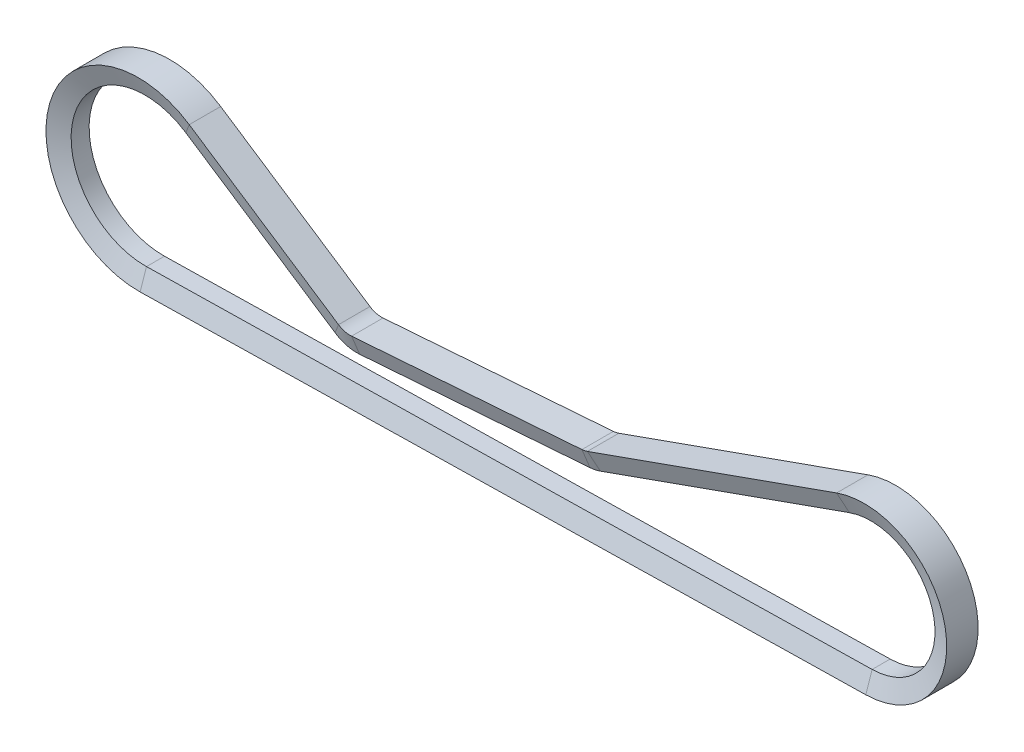
SolidWorks part; units mm, degrees
ref_plane "Front Plane" through (0, 0, 0) normal (0, 0, 1) x (1, 0, 0)
ref_plane "Top Plane" through (0, 0, 0) normal (0, 1, 0) x (1, 0, 0)
ref_plane "Right Plane" through (0, 0, 0) normal (1, 0, 0) x (0, 0, -1)
sketch "Sketch2" plane through (0, 0, 0) normal (0, 0, 1) x (1, 0, 0)
  line L0 (0, 0) -> (1, 0) construction
  line L1 (0, 0) -> (0, 1) construction
  line L12 (0.4814, -24.9954) -> (-219.4574, -29.231)
  line L14 (-204.5678, 22.1295) -> (-159.3267, -7.744)
  line L15 (-155.3616, -8.7779) -> (-85.5504, -3.6396)
  line L16 (-83.8896, -3.2899) -> (-8.3741, 23.5558)
  arc A4 (-219.4574, -29.231) -> (-204.5678, 22.1295) centre (-219.9965, -1.2362) cw
  arc A7 (-8.3741, 23.5558) -> (0.4814, -24.9954) centre (0, 0) cw
  arc A8 (-159.3267, -7.744) -> (-155.3616, -8.7779) centre (-155.8277, -2.445) ccw
  arc A9 (-85.5504, -3.6396) -> (-83.8896, -3.2899) centre (-86.0166, 2.6933) ccw
ref_plane "Plane4" through (-8.3741, 23.5558, 0) normal (0.9422, 0.335, 0) x (0.335, -0.9422, 0)
sketch "Sketch3" plane through (-8.3741, 23.5558, 0) normal (0.9422, 0.335, 0) x (0.335, -0.9422, 0)
  line L0 (0, -4.7625) -> (0, 4.7625)
  line L1 (0, -4.7625) -> (5.588, -2.7286)
  line L2 (5.588, -2.7286) -> (5.588, 2.7286)
  line L3 (5.588, 2.7286) -> (0, 4.7625)
  line L4 (0, 0) -> (5.588, 0) construction
  dimension "D1" = 9.525
  dimension "D2" = 5.588
  dimension "D3" = 40
sweep "Sweep1" add profiles "Sketch3" path "Sketch2"
